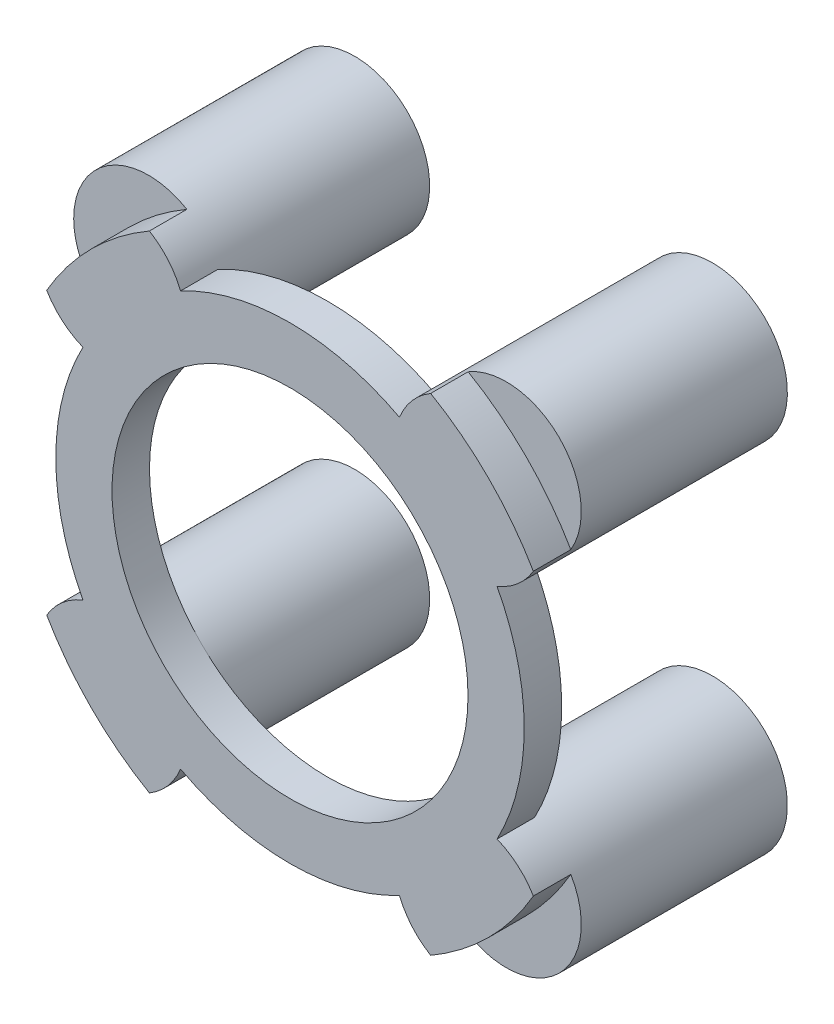
SolidWorks part; units mm, degrees
ref_plane "Front Plane" through (0, 0, 0) normal (0, 0, 1) x (1, 0, 0)
ref_plane "Top Plane" through (0, 0, 0) normal (0, 1, 0) x (1, 0, 0)
ref_plane "Right Plane" through (0, 0, 0) normal (1, 0, 0) x (0, 0, -1)
ref_plane "Output Plane" through (0, 0, 15) normal (0, 0, -1) x (-1, 0, 0)
sketch "CYC Output Sketch" plane through (0, 0, 15) normal (0, 0, 1) x (1, 0, 0)
  line L1 (9.5459, 9.5459) -> (-9.5459, 9.5459) construction
  line L2 (-9.5459, 9.5459) -> (-9.5459, -9.5459) construction
  line L3 (-9.5459, -9.5459) -> (9.5459, -9.5459) construction
  line L4 (9.5459, -9.5459) -> (9.5459, 9.5459) construction
  circle A0 centre (0, 0) radius 13.5 construction
sketch "Sketch3" plane through (0, 0, 15) normal (0, 0, -1) x (-1, 0, 0)
  circle A0 centre (-9.5459, 9.5459) radius 4
  circle A1 centre (9.5459, 9.5459) radius 4
  circle A2 centre (9.5459, -9.5459) radius 4
  circle A3 centre (-9.5459, -9.5459) radius 4
  dimension "D1" = 8
extrude "Boss-Extrude1" add sketch "Sketch3" along normal blind 11
sketch "Sketch6" plane through (0, 0, 15) normal (0, 0, 1) x (1, 0, 0)
  arc A0 (-7.5062, 12.9868) -> (-12.9868, 7.5062) centre (0, 0) ccw
  arc A5 (-11.0518, 5.8402) -> (-11.0518, -5.8402) centre (0, 0) ccw
  circle A6 centre (0, 0) radius 9.5
  arc A7 (-5.8402, 11.0518) -> (-7.5062, 12.9868) centre (-9.5459, 9.5459) ccw
  arc A8 (11.0518, 5.8402) -> (12.9868, 7.5062) centre (9.5459, 9.5459) ccw
  arc A9 (5.8402, -11.0518) -> (7.5062, -12.9868) centre (9.5459, -9.5459) ccw
  arc A10 (-11.0518, -5.8402) -> (-12.9868, -7.5062) centre (-9.5459, -9.5459) ccw
  arc A11 (5.8402, 11.0518) -> (-5.8402, 11.0518) centre (0, 0) ccw
  arc A12 (11.0518, -5.8402) -> (11.0518, 5.8402) centre (0, 0) ccw
  arc A13 (-5.8402, -11.0518) -> (5.8402, -11.0518) centre (0, 0) ccw
  arc A14 (7.5062, 12.9868) -> (5.8402, 11.0518) centre (9.5459, 9.5459) ccw
  arc A15 (12.9868, -7.5062) -> (11.0518, -5.8402) centre (9.5459, -9.5459) ccw
  arc A16 (-7.5062, -12.9868) -> (-5.8402, -11.0518) centre (-9.5459, -9.5459) ccw
  arc A17 (-12.9868, 7.5062) -> (-11.0518, 5.8402) centre (-9.5459, 9.5459) ccw
  arc A18 (12.9868, 7.5062) -> (7.5062, 12.9868) centre (0, 0) ccw
  arc A19 (7.5062, -12.9868) -> (12.9868, -7.5062) centre (0, 0) ccw
  arc A20 (-12.9868, -7.5062) -> (-7.5062, -12.9868) centre (0, 0) ccw
  dimension "D2" = 30
  dimension "D3" = 25
  dimension "D4" = 8
  dimension "D1" = 19
  dimension "D5" = 27
extrude "Boss-Extrude6" add sketch "Sketch6" along normal blind 2 contours A6 | A0 A17 A5 A10 A20 A16 A13 A9 A19 A15 A12 A8 A18 A14 A11 A7 region at (0, 0, 15)
equation "\"RingPinShaft\"= 5"
equation "\"CenterBearingOut\"=32"
equation "\"RingPostIn\"=5"
equation "\"CamBearingOut\"=15.15"
equation "\"DiskOutputShaft\"=10"
equation "\"CenterShaft\"=25"
equation "\"Eccentricity\"=2"
equation "\"CycCamShaft\"=10"
equation "\"D2@Sketch6\"=\"OutputBearing\""
equation "\"OutputBearing\"=30"
